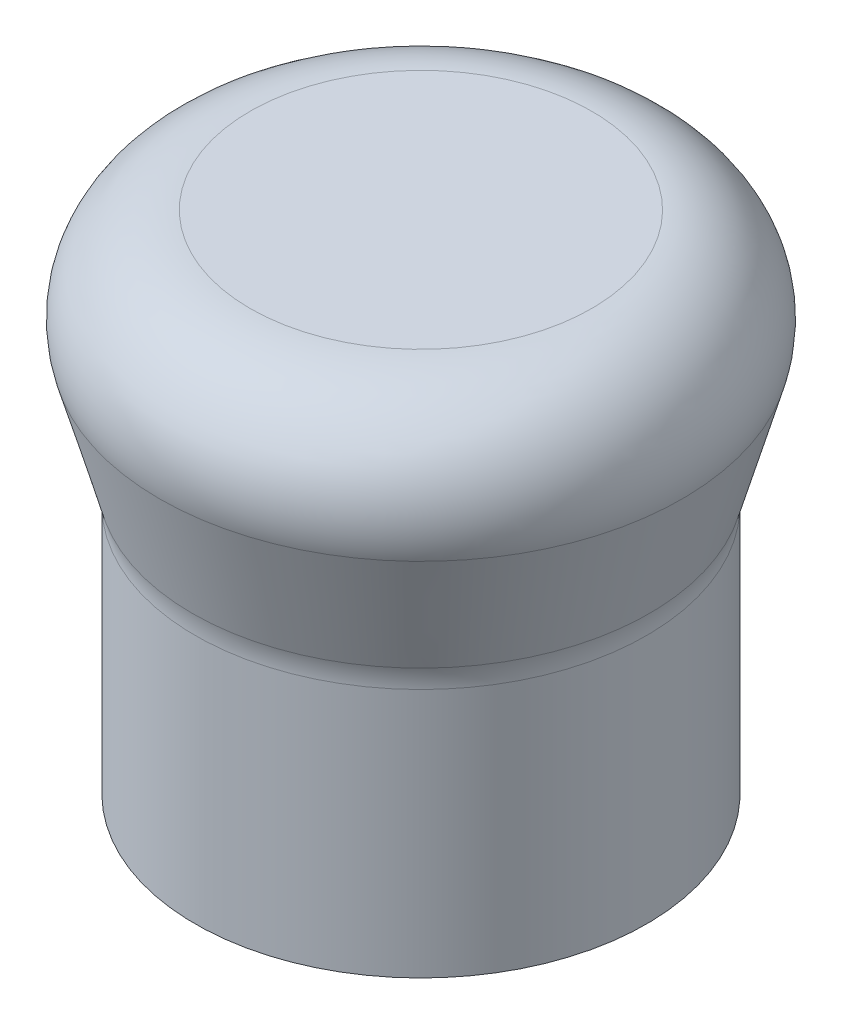
SolidWorks part; units mm, degrees
material "Plastique personnalisé"
ref_plane "Plan de face" through (0, 0, 0) normal (0, 0, 1) x (1, 0, 0)
ref_plane "Plan de dessus" through (0, 0, 0) normal (0, 1, 0) x (1, 0, 0)
ref_plane "Plan de droite" through (0, 0, 0) normal (1, 0, 0) x (0, 0, -1)
sketch "Esquisse1" plane through (0, 0, 0) normal (0, 0, 1) x (1, 0, 0)
  line L1 (10, 0) -> (10, 7.0605)
  line L2 (10, 7.0605) -> (11.5286, 12.4468)
  line L3 (5, 0) -> (5, 24.8937) construction
  line L4 (11.5286, 12.4468) -> (5, 12.4468)
  line L5 (5, 12.4468) -> (5, 0)
  line L6 (5, 0) -> (10, 0)
revolve "Révolution1" add sketch "Esquisse1" angle 360 about L3
fillet "Congé1" radius 1.5 1 edges at (5, 12.4468, -6.5286)
fillet "Congé2" radius 3 1 edges at (5, 7.0605, -5)
shell "Coque1" thickness 1 removed face at (5, 0, -5) outward yes
